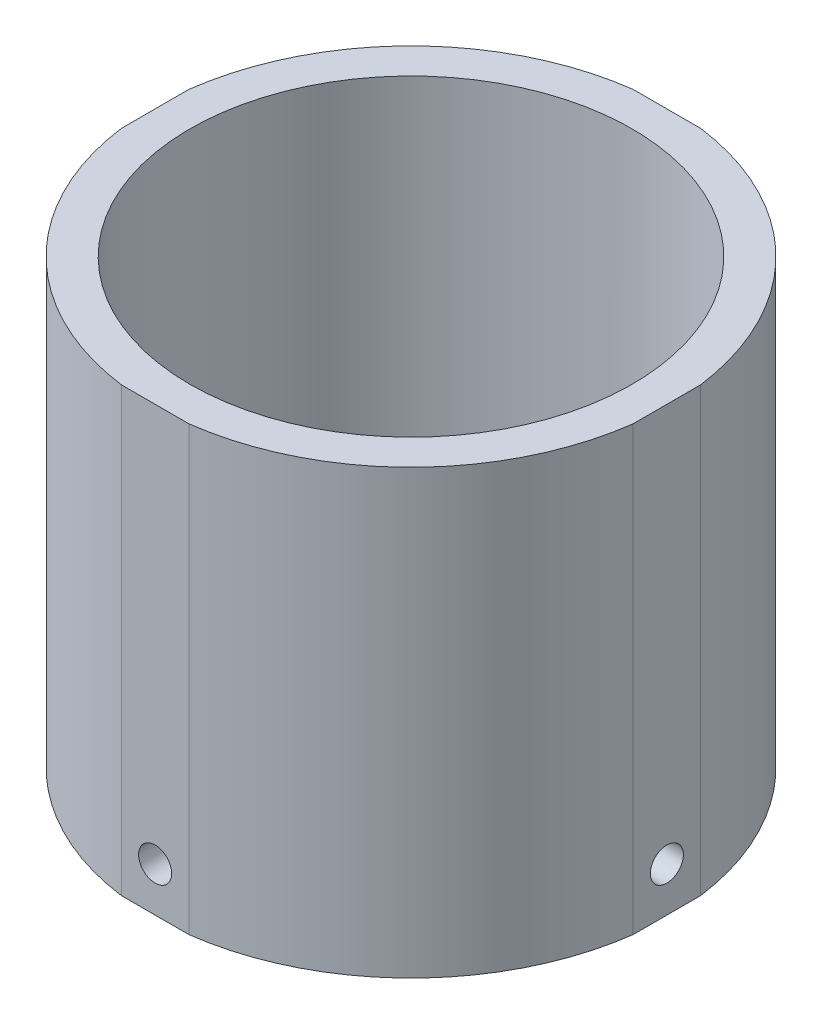
SolidWorks part; units mm, degrees
material "6061 Alloy"
ref_plane "Front Plane" through (0, 0, 0) normal (0, 0, 1) x (1, 0, 0)
ref_plane "Top Plane" through (0, 0, 0) normal (0, 1, 0) x (1, 0, 0)
ref_plane "Right Plane" through (0, 0, 0) normal (1, 0, 0) x (0, 0, -1)
sketch "Sketch1" plane through (0, 0, 0) normal (0, 1, 0) x (1, 0, 0)
  circle A0 centre (0, 0) radius 22.225
  circle A1 centre (0, 0) radius 19.05
  dimension "D1" = 44.45
  dimension "D2" = 3.175
extrude "Boss-Extrude1" add sketch "Sketch1" along normal blind 38.1
sketch "Sketch2" plane through (0, 0, 0) normal (0, 0, 1) x (1, 0, 0)
  line L0 (0, 0) -> (0, 3.81) construction
  circle A0 centre (0, 3.81) radius 1.4224
  dimension "D1" = 2.8448
  dimension "D2" = 3.81
extrude "Cut-Extrude1" cut sketch "Sketch2" against normal blind 43.18 and the other way blind 43.18
sketch "Sketch3" plane through (0, 0, 0) normal (1, 0, 0) x (0, 0, -1)
  line L0 (0, 0) -> (0, 3.81) construction
  circle A0 centre (0, 3.81) radius 1.4224
  dimension "D1" = 2.8448
extrude "Cut-Extrude2" cut sketch "Sketch3" against normal blind 43.18 and the other way blind 43.18
sketch "Sketch4" plane through (0, 0, 0) normal (0, -1, 0) x (1, 0, 0)
  line L1 (22.0345, -22.0345) -> (-22.0345, -22.0345)
  line L2 (22.0345, -22.0345) -> (22.0345, 22.0345)
  line L3 (22.0345, 22.0345) -> (-22.0345, 22.0345)
  line L4 (-22.0345, -22.0345) -> (-22.0345, 22.0345)
  line L5 (22.0345, -22.0345) -> (-22.0345, 22.0345) construction
  line L6 (22.0345, 22.0345) -> (-22.0345, -22.0345) construction
  line L7 (24.5128, -24.0002) -> (-24.5128, -24.0002)
  line L8 (24.5128, -24.0002) -> (24.5128, 24.0002)
  line L9 (24.5128, 24.0002) -> (-24.5128, 24.0002)
  line L10 (-24.5128, -24.0002) -> (-24.5128, 24.0002)
  line L11 (24.5128, -24.0002) -> (-24.5128, 24.0002) construction
  line L12 (24.5128, 24.0002) -> (-24.5128, -24.0002) construction
  point P0 (0, 0)
  point P6 (0, 0)
  dimension "D1" = 44.069
  dimension "D2" = 44.069
extrude "Cut-Extrude3" cut sketch "Sketch4" against normal blind 43.18
